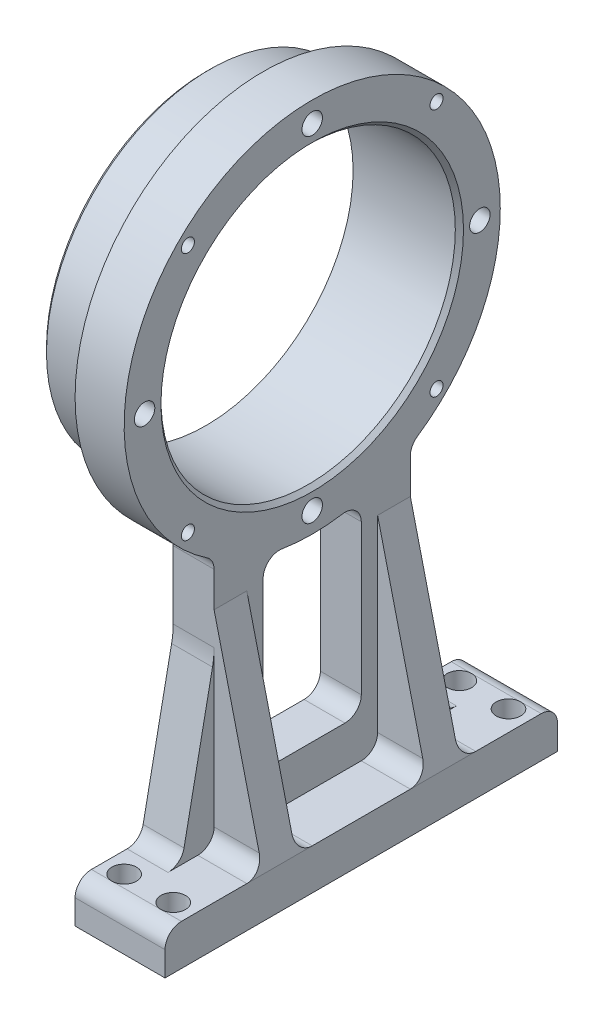
SolidWorks part; units mm, degrees
material "6061-T6 (SS)"
ref_plane "前视基准面" through (0, 0, 0) normal (0, 0, 1) x (1, 0, 0)
ref_plane "上视基准面" through (0, 0, 0) normal (0, 1, 0) x (1, 0, 0)
ref_plane "右视基准面" through (0, 0, 0) normal (1, 0, 0) x (0, 0, -1)
sketch "草图3" plane through (0, 0, 0) normal (0, 0, 1) x (1, 0, 0)
  line L0 (-123.6471, 0) -> (148.9722, 0) construction
  line L1 (0, 129.3178) -> (0, -130.5225) construction
  line L2 (6, 18) -> (-7, 18)
  line L3 (-7, 18) -> (-7, 20)
  line L4 (-7, 20) -> (0, 20)
  line L5 (0, 20) -> (0, 23)
  line L6 (0, 23) -> (6, 23)
  line L7 (6, 23) -> (6, 18)
  dimension "D1" = 40
  dimension "D2" = 2
  dimension "D3" = 7
  dimension "D4" = 6
  dimension "D5" = 46
revolve "旋转1" add sketch "草图3" angle 360 about L0
sketch "草图4" plane through (6, 0, 0) normal (1, 0, 0) x (0, 0, -1)
  line L0 (0, 56.9178) -> (0, -67.9112) construction
  line L1 (-57.6217, 0) -> (73.1723, 0) construction
  line L2 (-12, -30) -> (-12, -19.6214)
  line L3 (-12, -30) -> (-16, -50)
  line L4 (-16, -50) -> (-24, -50)
  line L5 (-24, -50) -> (-24, -55)
  line L6 (-24, -55) -> (24, -55)
  line L7 (24, -50) -> (24, -55)
  line L8 (16, -50) -> (24, -50)
  line L9 (12, -30) -> (16, -50)
  line L10 (12, -30) -> (12, -19.6214)
  line L13 (-6, -22.2036) -> (-6, -45)
  line L14 (-6, -45) -> (6, -45)
  line L15 (6, -22.2036) -> (6, -45)
  line L16 (-6, -22.2036) -> (6, -45) construction
  line L17 (-6, -45) -> (6, -22.2036) construction
  circle A0 centre (0, 0) radius 23 construction
  arc A1 (-12, -19.6214) -> (12, -19.6214) centre (0, 0) ccw
  arc A2 (23, 0) -> (-23, 0) centre (0, 0) ccw
  point P15 (0, -55)
  point P22 (0, -33.6018)
  circle M17 centre (0, 0) radius 23
  dimension "D1" = 48
  dimension "D2" = 8
  dimension "D3" = 5
  dimension "D4" = 55
  dimension "D5" = 24
  dimension "D6" = 25
  dimension "D7" = 6
  dimension "D8" = 10
extrude "凸台-拉伸1" add sketch "草图4" against normal blind 5 contours L15 L14 L13 L2 L3 L4 L5 L6 L7 L8 L9 L10 M17
sketch "草图16" plane through (1, 0, 0) normal (1, 0, 0) x (0, 0, -1)
  line L0 (-24, -50) -> (-24, -55) construction
  line L1 (-24, -50) -> (-24, -55)
  line L2 (-24, -55) -> (24, -55) construction
  line L3 (-24, -55) -> (24, -55)
  line L4 (24, -50) -> (24, -55) construction
  line L5 (24, -50) -> (24, -55)
  line L6 (-24, -50) -> (24, -50)
extrude "凸台-拉伸3" add sketch "草图16" along normal blind 11
sketch "草图5" plane through (0, -55, 0) normal (0, -1, 0) x (1, 0, 0)
  line L0 (32.8001, 0) -> (-29.1426, 0) construction
  line L1 (6.5, 24) -> (6.5, -24) construction
  line L5 (1, -24) -> (12, -24) construction
  line L6 (12, 24) -> (12, -24) construction
  circle A0 centre (9.5, 20.5) radius 1.5
  circle A1 centre (9.5, -20.5) radius 1.5
  circle A2 centre (3.5, -20.5) radius 1.5
  circle A3 centre (3.5, 20.5) radius 1.5
  point P9 (6.5, 20.5)
  point P10 (6.5, -20.5)
  point P12 (6.5, -24)
  dimension "D2" = 3
  dimension "D1" = 41
  dimension "D3" = 2.5
extrude "切除-拉伸4" cut sketch "草图5" against normal up to next
sketch "草图17" plane through (0, 0, 12) normal (0, 0, 1) x (1, 0, 0)
  line L0 (6, -25) -> (12, -50)
  line L2 (1, -50) -> (12, -50) construction
  line L3 (1, -50) -> (12, -50) construction
  line L4 (6, -30) -> (6, -19.6214) construction
  dimension "D1" = 25
rib "筋1" sketch "草图17" sketch "草图17" thickness 4 extrusion direction parallel to sketch draft on no parameters "D1"=4
mirror "镜向1" about plane through (0, 0, 0) normal (0, 0, 1) of "筋1"
hole_wizard "Ø3.0 (3) 直径孔1" [suppressed] positions "草图6" profile "草图7" hole size "Ø3.0" standard "GB"
sketch "草图6" plane through (0, -55, 0) normal (0, -1, 0) x (-1, 0, 0)
  point P0 (-3, -20.5)
  point P3 (-3, 20.5)
sketch "草图7" plane through (3, -55, 20.5) normal (1, 0, 0) x (0, 0, -1)
  line L0 (0, 0) -> (0, 5)
  line L1 (0, 5) -> (1.5, 5)
  line L2 (1.5, 5) -> (1.5, 0)
  line L5 (1.5, 0) -> (0, 0)
  line L11 (0, -6.35) -> (0, 107.95) construction
  dimension "通孔孔直径" = 3
  dimension "通孔孔深度" = 5
fillet "圆角1" radius 2 14 edges at (3.5, -19.6214, -12) (3.5, -19.6214, 12) (3.5, -22.2036, -6) (3.5, -22.2036, 6) (3.5, -45, -6) (3.5, -45, 6) (6.5, -50, 24) (3.5, -50, 16) (6.5, -50, -24) (3.5, -50, -16) (9, -50, -12) (9, -50, -8) (9, -50, 8) (9, -50, 12)
sketch "草图8" plane through (6, 0, 0) normal (1, 0, 0) x (0, 0, -1)
  circle A0 centre (0, 0) radius 20.5 construction
  point P3 (0, 20.5)
  point P7 (20.5, 0)
  point P8 (0, -20.5)
  point P9 (-20.5, 0)
  point P10 (0, 0)
  dimension "D1" = 41
  dimension "D2" = 4
hole_wizard "M3 螺纹孔2" positions "草图9" profile "草图10" tap size "M3" standard "GB"
sketch "草图9" plane through (6, 0, 0) normal (1, 0, 0) x (0, 0, -1)
  point P0 (0, 20.5)
  point P3 (-20.5, 0)
  point P6 (0, -20.5)
  point P9 (20.5, 0)
sketch "草图10" plane through (6, 20.5, 0) normal (0, 1, 0) x (0, 0, -1)
  line L0 (0, 0) -> (0, 5.7511)
  line L1 (0, 5.7511) -> (1.25, 5)
  line L2 (1.25, 5) -> (1.25, 0)
  line L5 (1.25, 0) -> (0, 0)
  line L10 (0, 5.7511) -> (-1.25, 5) construction
  line L11 (0, -6.35) -> (0, 107.95) construction
  dimension "螺纹孔钻头直径" = 2.5
  dimension "螺纹孔钻头深度" = 5
  dimension "导头角度" = 118
cosmetic thread "孔螺蚊线3" parameters "D1"=5, "D2"=3
cosmetic thread "孔螺蚊线4" parameters "D1"=5, "D2"=3
cosmetic thread "孔螺蚊线5" parameters "D1"=5, "D2"=3
cosmetic thread "孔螺蚊线6" parameters "D1"=5, "D2"=3
sketch "草图11" plane through (6, 0, 0) normal (1, 0, 0) x (0, 0, -1)
  line L0 (0, 0) -> (33.9072, 0) construction
  line L1 (0, 0) -> (20.7265, 20.7265) construction
  circle A0 centre (0, 0) radius 21.5 construction
  point P3 (15.2028, 15.2028)
  point P9 (15.2028, -15.2028)
  point P10 (-15.2028, -15.2028)
  point P11 (-15.2028, 15.2028)
  point P12 (0, 0)
  dimension "D1" = 45
  dimension "D2" = 43
  dimension "D3" = 4
hole_wizard "M2 螺纹孔1" positions "草图12" profile "草图13" tap size "M2" standard "GB" end condition through all
sketch "草图12" plane through (6, 0, 0) normal (1, 0, 0) x (0, 0, -1)
  point P0 (-15.2028, 15.2028)
  point P3 (15.2028, 15.2028)
  point P6 (15.2028, -15.2028)
  point P9 (-15.2028, -15.2028)
sketch "草图13" plane through (6, 15.2028, 15.2028) normal (0, 1, 0) x (0, 0, -1)
  line L0 (0, 0) -> (0, 13)
  line L1 (0, 13) -> (0.8, 13)
  line L2 (0.8, 13) -> (0.8, 0)
  line L5 (0.8, 0) -> (0, 0)
  line L11 (0, -6.35) -> (0, 107.95) construction
  dimension "通孔螺纹孔钻头直径" = 1.6
  dimension "通孔螺纹孔钻头深度" = 13
cosmetic thread "孔螺蚊线7" parameters "D2"=2
cosmetic thread "孔螺蚊线8" parameters "D2"=2
cosmetic thread "孔螺蚊线9" parameters "D2"=2
cosmetic thread "孔螺蚊线10" parameters "D2"=2
chamfer "倒角1" distance 0.5 angle 45 2 edges at (6, 0, 18) (-7, 0, 20)
move or copy body "实体-移动/复制1" bodies to move or copy 110
fillet "圆角2" radius 10 2 edges at (3.5, -30, -12) (3.5, -30, 12)
